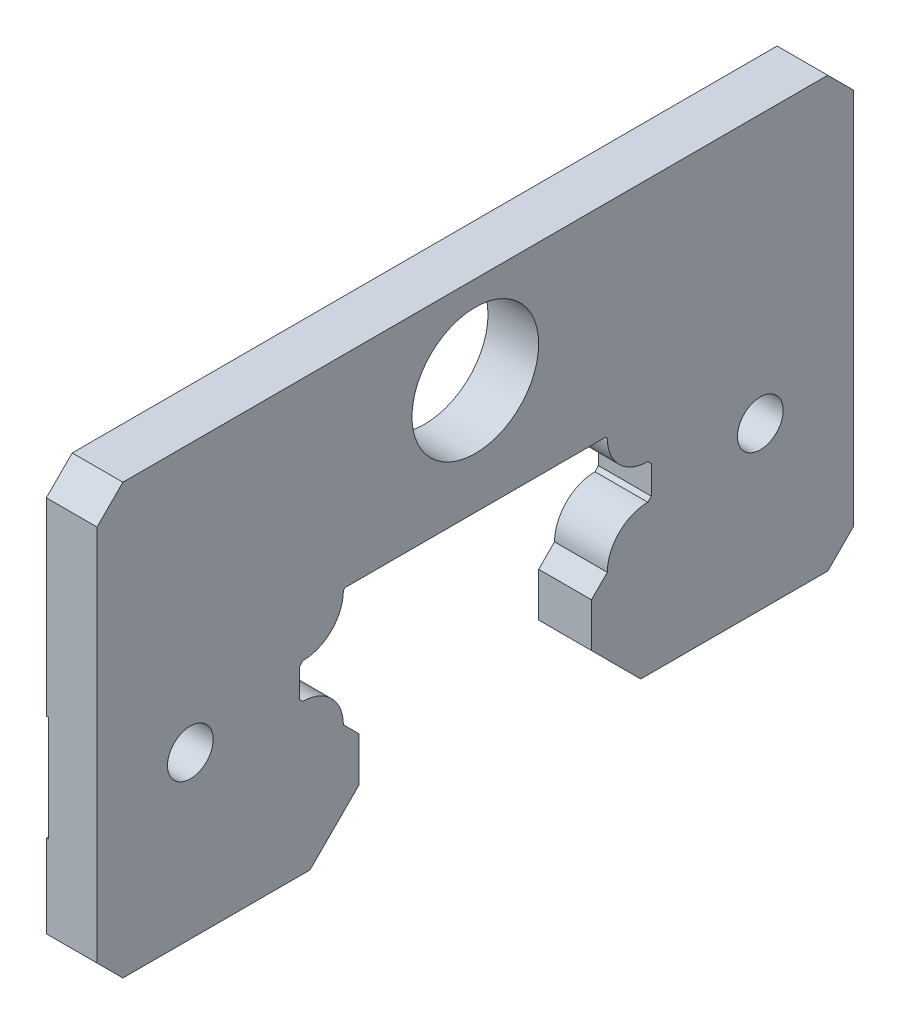
SolidWorks part; units mm, degrees
ref_plane "Спереди" through (0, 0, 0) normal (0, 0, 1) x (1, 0, 0)
ref_plane "Сверху" through (0, 0, 0) normal (0, 1, 0) x (1, 0, 0)
ref_plane "Сбоку" through (0, 0, 0) normal (1, 0, 0) x (0, 0, -1)
ref_plane "Плоскость1" through (0, 0, 0) normal (1, 0, 0) x (0, 0, -1)
sketch "Эскиз1" plane through (0, 0, 0) normal (1, 0, 0) x (0, 0, -1)
  line L0 (-21.5, 22.9292) -> (-21.5, 1.4708)
  line L1 (-21.5, 1.4708) -> (-20.0292, 0)
  line L2 (-20.0292, 0) -> (20.0292, 0)
  line L3 (20.0292, 0) -> (21.5, 1.4708)
  line L4 (21.5, 1.4708) -> (21.5, 22.9292)
  line L5 (21.5, 22.9292) -> (20.0292, 24.4)
  line L6 (20.0292, 24.4) -> (-20.0292, 24.4)
  line L7 (-20.0292, 24.4) -> (-21.5, 22.9292)
extrude "Бобышка-Вытянуть1" add sketch "Эскиз1" against normal blind 1.5 and the other way blind 1.5
ref_plane "Плоскость2" through (0, 0, 0) normal (1, 0, 0) x (0, 0, -1)
sketch "Эскиз2" plane through (0, 0, 0) normal (1, 0, 0) x (0, 0, -1)
  line L0 (-14, -4.6) -> (14, -4.6)
  line L1 (14, -4.6) -> (6.6, 2.8)
  line L2 (6.6, 2.8) -> (6.6, 5.3)
  line L3 (6.6, 5.3) -> (7.5, 6.2)
  line L4 (9.8, 8.5) -> (10, 8.7)
  line L5 (10, 8.7) -> (10, 10.3)
  line L6 (10, 10.3) -> (9.8, 10.5)
  line L7 (7.5, 12.8) -> (7.4, 12.9)
  line L8 (7.4, 12.9) -> (-7.4, 12.9)
  line L9 (-7.4, 12.9) -> (-7.5, 12.8)
  line L10 (-9.8, 10.5) -> (-10, 10.3)
  line L11 (-10, 10.3) -> (-10, 8.7)
  line L12 (-10, 8.7) -> (-9.8, 8.5)
  line L13 (-7.5, 6.2) -> (-6.6, 5.3)
  line L14 (-6.6, 5.3) -> (-6.6, 2.8)
  line L15 (-6.6, 2.8) -> (-14, -4.6)
  arc A0 (7.5, 6.2) -> (9.8, 8.5) centre (9.8, 6.2) cw
  arc A1 (9.8, 10.5) -> (7.5, 12.8) centre (9.8, 12.8) cw
  arc A2 (-7.5, 12.8) -> (-9.8, 10.5) centre (-9.8, 12.8) cw
  arc A3 (-9.8, 8.5) -> (-7.5, 6.2) centre (-9.8, 6.2) cw
extrude "Вырез-Вытянуть1" cut sketch "Эскиз2" against normal blind 1.5 and the other way blind 1.5
ref_plane "Плоскость3" through (-1.5, 0, 0) normal (1, 0, 0) x (0, 0, -1)
sketch "Эскиз3" plane through (-1.5, 0, 0) normal (1, 0, 0) x (0, 0, -1)
  line L0 (-21.5, -4.6) -> (-15.4142, -4.6)
  line L1 (-15.4142, -4.6) -> (-7.6, 3.2142)
  line L2 (-7.6, 3.2142) -> (-7.6, 4.8858)
  line L3 (-7.6, 4.8858) -> (-8.2071, 5.4929)
  line L4 (-10.5071, 7.7929) -> (-11, 8.2858)
  line L5 (-11, 8.2858) -> (-11, 10.7142)
  line L6 (-11, 10.7142) -> (-10.5071, 11.2071)
  line L7 (-8.2071, 13.5071) -> (-7.8142, 13.9)
  line L8 (-7.8142, 13.9) -> (7.8142, 13.9)
  line L9 (7.8142, 13.9) -> (8.2071, 13.5071)
  line L10 (10.5071, 11.2071) -> (11, 10.7142)
  line L11 (11, 10.7142) -> (11, 8.2858)
  line L12 (11, 8.2858) -> (10.5071, 7.7929)
  line L13 (8.2071, 5.4929) -> (7.6, 4.8858)
  line L14 (7.6, 4.8858) -> (7.6, 3.2142)
  line L15 (7.6, 3.2142) -> (15.4142, -4.6)
  line L16 (15.4142, -4.6) -> (21.5, -4.6)
  line L17 (21.5, -4.6) -> (21.5, 24.4)
  line L18 (21.5, 24.4) -> (-21.5, 24.4)
  line L19 (-21.5, 24.4) -> (-21.5, -4.6)
  arc A0 (-8.2071, 5.4929) -> (-10.5071, 7.7929) centre (-10.5071, 5.4929) ccw
  arc A1 (-10.5071, 11.2071) -> (-8.2071, 13.5071) centre (-10.5071, 13.5071) ccw
  arc A2 (8.2071, 13.5071) -> (10.5071, 11.2071) centre (10.5071, 13.5071) ccw
  arc A3 (10.5071, 7.7929) -> (8.2071, 5.4929) centre (10.5071, 5.4929) ccw
extrude "Вырез-Вытянуть2" cut sketch "Эскиз3" along normal blind 0.12
ref_plane "Плоскость4" through (-1.5, 0, 0) normal (1, 0, 0) x (0, 0, -1)
sketch "Эскиз4" plane through (-1.5, 0, 0) normal (1, 0, 0) x (0, 0, -1)
  circle A0 centre (0, 19.4) radius 3.6
extrude "Вырез-Вытянуть3" cut sketch "Эскиз4" along normal blind 3
ref_plane "Плоскость5" through (-1.5, 0, 0) normal (1, 0, 0) x (0, 0, -1)
sketch "Эскиз5" plane through (-1.5, 0, 0) normal (1, 0, 0) x (0, 0, -1)
  line L0 (-21.5, 6.1852) -> (-16.0679, 6.1852)
  line L1 (-16.3234, 12.1852) -> (-21.5, 12.1852)
  line L2 (-21.5, 12.1852) -> (-21.5, 6.1852)
  arc A0 (-16.0679, 6.1852) -> (-16.3234, 12.1852) centre (-16.1957, 9.1852) ccw
extrude "Вырез-Вытянуть4" cut sketch "Эскиз5" along normal blind 0.24
ref_plane "Плоскость6" through (-1.5, 0, 0) normal (1, 0, 0) x (0, 0, -1)
sketch "Эскиз6" plane through (-1.5, 0, 0) normal (1, 0, 0) x (0, 0, -1)
  line L0 (16.0679, 6.1852) -> (21.5, 6.1852)
  line L1 (21.5, 6.1852) -> (21.5, 12.1852)
  line L2 (21.5, 12.1852) -> (16.3234, 12.1852)
  arc A0 (16.3234, 12.1852) -> (16.0679, 6.1852) centre (16.1957, 9.1852) ccw
extrude "Вырез-Вытянуть5" cut sketch "Эскиз6" along normal blind 0.24
ref_plane "Плоскость7" through (0, 0, 0) normal (1, 0, 0) x (0, 0, -1)
sketch "Эскиз7" plane through (0, 0, 0) normal (1, 0, 0) x (0, 0, -1)
  circle A0 centre (-16.1957, 9.1852) radius 1.3
extrude "Вырез-Вытянуть6" cut sketch "Эскиз7" against normal blind 3 and the other way blind 3
ref_plane "Плоскость8" through (0, 0, 0) normal (1, 0, 0) x (0, 0, -1)
sketch "Эскиз8" plane through (0, 0, 0) normal (1, 0, 0) x (0, 0, -1)
  circle A0 centre (16.1957, 9.1852) radius 1.3
extrude "Вырез-Вытянуть7" cut sketch "Эскиз8" against normal blind 3 and the other way blind 3
